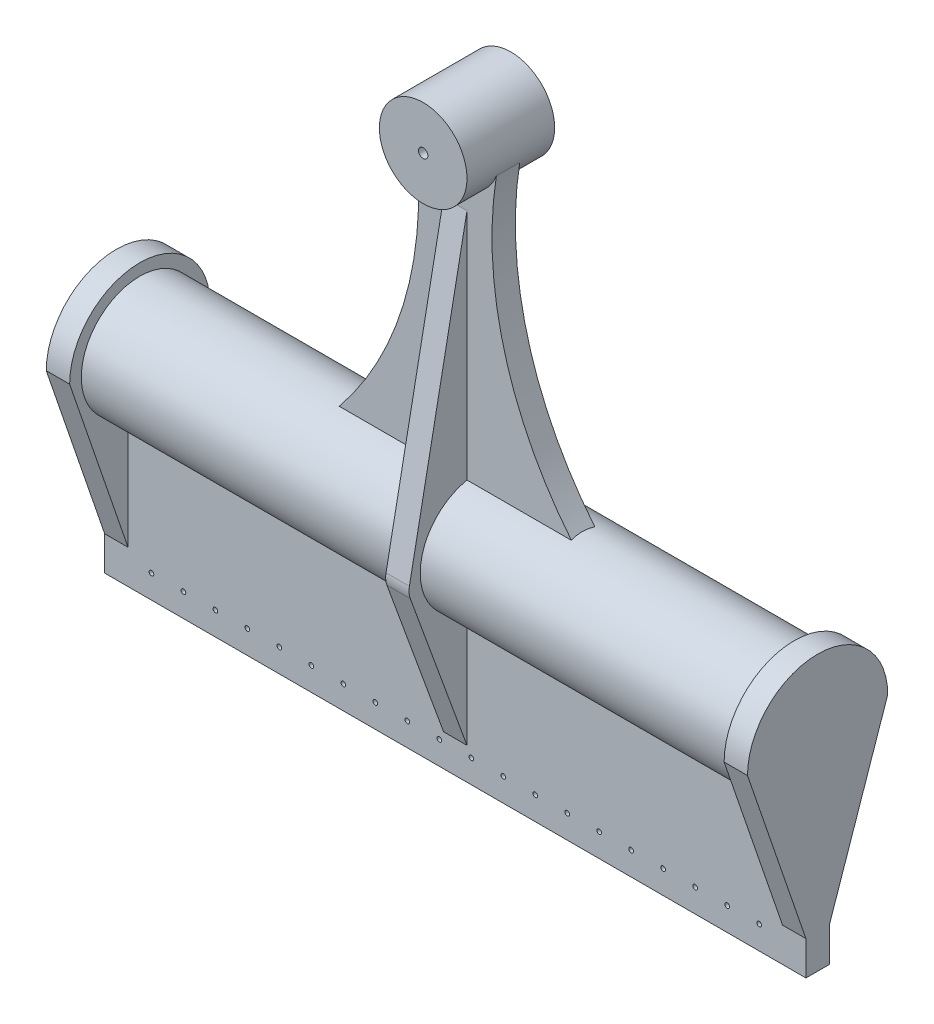
SolidWorks part; units mm, degrees
ref_plane "Front Plane" through (0, 0, 0) normal (1, 0, 0) x (0, 1, 0)
ref_plane "Top Plane" through (0, 0, 0) normal (0, 0, 1) x (0, 1, 0)
ref_plane "Right Plane" through (0, 0, 0) normal (0, 1, 0) x (-1, 0, 0)
sketch "Sketch1" plane through (0, 0, 0) normal (0, 0, 1) x (0, 1, 0)
  line L1 (-44.45, -76.2) -> (0, -76.2)
  line L2 (-44.45, -76.2) -> (-44.45, 76.2)
  line L3 (-44.45, 76.2) -> (0, 76.2)
  line L4 (0, -76.2) -> (0, 76.2)
  line L5 (-44.45, -76.2) -> (0, 76.2) construction
  line L6 (-44.45, 76.2) -> (0, -76.2) construction
  circle A0 centre (-39.37, -66.04) radius 0.508
  circle A1 centre (-39.37, -59.0884) radius 0.508
  circle A2 centre (-39.37, -52.1368) radius 0.508
  circle A3 centre (-39.37, -45.1853) radius 0.508
  circle A4 centre (-39.37, -38.2337) radius 0.508
  circle A5 centre (-39.37, -31.2821) radius 0.508
  circle A6 centre (-39.37, -24.3305) radius 0.508
  circle A7 centre (-39.37, -17.3789) radius 0.508
  circle A8 centre (-39.37, -10.4274) radius 0.508
  circle A9 centre (-39.37, -3.4758) radius 0.508
  circle A10 centre (-39.37, 3.4758) radius 0.508
  circle A11 centre (-39.37, 10.4274) radius 0.508
  circle A12 centre (-39.37, 17.3789) radius 0.508
  circle A13 centre (-39.37, 24.3305) radius 0.508
  circle A14 centre (-39.37, 31.2821) radius 0.508
  circle A15 centre (-39.37, 38.2337) radius 0.508
  circle A16 centre (-39.37, 45.1853) radius 0.508
  circle A17 centre (-39.37, 52.1368) radius 0.508
  circle A18 centre (-39.37, 59.0884) radius 0.508
  circle A19 centre (-39.37, 66.04) radius 0.508
  point P0 (-22.225, 0)
extrude "Boss-Extrude1" add sketch "Sketch1" along normal blind 2.54 and the other way blind 2.54
sketch "Sketch2" plane through (0, 0, 0) normal (1, 0, 0) x (0, 1, 0)
  circle A0 centre (0, 0) radius 12.7
extrude "Boss-Extrude2" add sketch "Sketch2" along normal blind 76.2 and the other way blind 76.2
sketch "Sketch3" plane through (0, 0, 0) normal (1, 0, 0) x (0, 1, 0)
  line L0 (0, 15.24) -> (-44.45, 0)
  line L1 (-44.45, 0) -> (0, -15.24)
  arc A0 (0, -15.24) -> (0, 15.24) centre (0, 0) ccw
extrude "Boss-Extrude3" add sketch "Sketch3" along normal blind 5.08 from offset 71.12
sketch "Sketch4" plane through (0, 0, 0) normal (1, 0, 0) x (0, 1, 0)
  line L0 (0, 15.24) -> (-44.45, 0)
  line L1 (-44.45, 0) -> (0, -15.24)
  arc A0 (0, -15.24) -> (0, 15.24) centre (0, 0) ccw
extrude "Boss-Extrude4" add sketch "Sketch4" against normal blind 5.08 from offset 71.12 offset against normal yes
sketch "Sketch5" plane through (0, 0, 0) normal (0, 0, 1) x (0, 1, 0)
  line L0 (0, -38.1) -> (0, 38.1)
  line L1 (76.2, 9.525) -> (76.2, -9.525)
  arc A0 (0, 38.1) -> (76.2, 9.525) centre (60.8501, 84.4794) ccw
  arc A1 (76.2, -9.525) -> (0, -38.1) centre (60.8501, -84.4794) ccw
extrude "Boss-Extrude5" add sketch "Sketch5" along normal blind 2.54 and the other way blind 2.54
sketch "Sketch6" plane through (0, 0, 0) normal (0, 0, 1) x (0, 1, 0)
  circle A0 centre (76.2, 0) radius 9.525
  circle A1 centre (76.2, 0) radius 1.016
extrude "Boss-Extrude6" add sketch "Sketch6" along normal blind 9.525 and the other way blind 9.525
sketch "Sketch7" plane through (0, 0, 0) normal (1, 0, 0) x (0, 1, 0)
  line L0 (-44.45, 0) -> (-3.7233, 14.8644)
  line L1 (-44.45, -2.54) -> (-44.45, 2.54) construction
  line L2 (-1.2894, 15.0571) -> (76.2, 0)
  line L3 (76.2, 0) -> (3.0481, -14.9321)
  line L4 (-12.1784, -13.4534) -> (-44.45, 0)
  arc A0 (-3.7233, 14.8644) -> (-1.2894, 15.0571) centre (-2.1595, 10.5796) cw
  arc A1 (0, -15.24) -> (0, 15.24) centre (0, 0) ccw construction
  arc A2 (3.0481, -14.9321) -> (-12.1784, -13.4534) centre (-2.1595, 10.5796) cw
extrude "Boss-Extrude7" add sketch "Sketch7" along normal blind 2.54 and the other way blind 2.54
